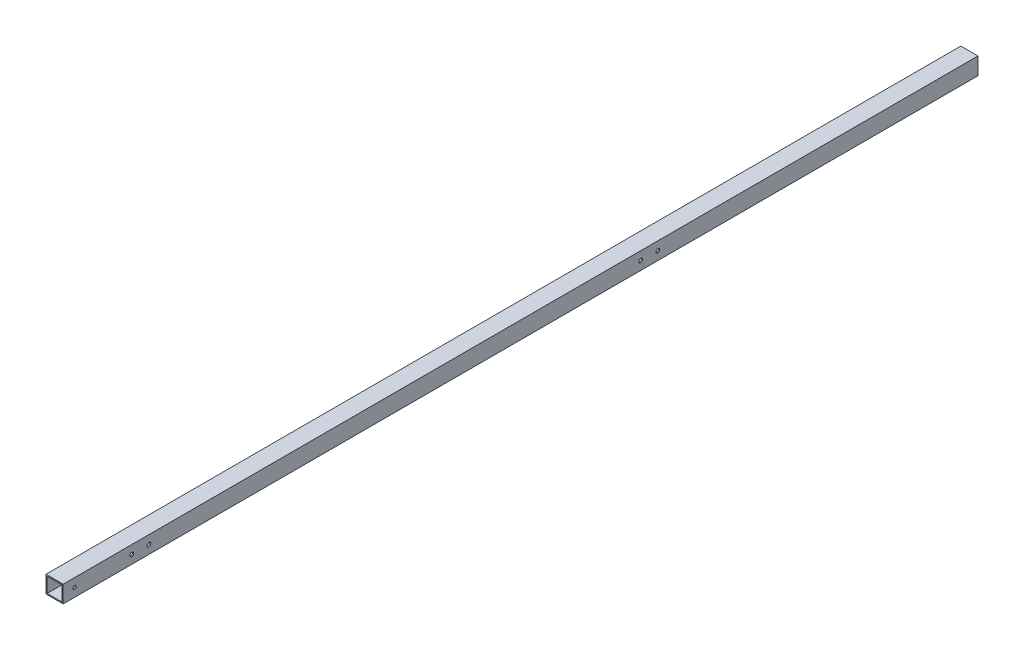
SolidWorks part; units mm, degrees
material "1060 合金"
ref_plane "前视基准面" through (0, 0, 0) normal (0, 0, 1) x (1, 0, 0)
ref_plane "上视基准面" through (0, 0, 0) normal (0, 1, 0) x (1, 0, 0)
ref_plane "右视基准面" through (0, 0, 0) normal (1, 0, 0) x (0, 0, -1)
other "Configuration Table"
sketch "草图1" plane through (0, 0, 0) normal (0, 0, 1) x (1, 0, 0)
  line L1 (0, 0) -> (15, 0)
  line L2 (0, 0) -> (0, -15)
  line L3 (0, -15) -> (15, -15)
  line L4 (15, 0) -> (15, -15)
  dimension "D1" = 15
  dimension "D2" = 15
extrude "拉伸-薄壁1" add sketch "草图1" along normal blind 800 thin thin type one direction reverse wall 1
sketch "草图2" plane through (0, -15, 0) normal (0, -1, 0) x (1, 0, 0)
  circle A1 centre (7.5, 825) radius 2.6
  circle A2 centre (7.5, 825) radius 2.6
  dimension "D1" = 0
extrude "切除-拉伸1" [suppressed] cut sketch "草图2" against normal up to next
sketch "草图3" plane through (0, 0, 0) normal (-1, 0, 0) x (0, 0, 1)
  line L0 (800, 0) -> (0, 0) construction
  line L1 (0, 0) -> (0, -15) construction
  circle A0 centre (215, -7.5) radius 1.7
  circle A1 centre (170, -7.5) radius 1.7
  dimension "D1" = 3.4
  dimension "D2" = 3.4
  dimension "D3" = 45
  dimension "D4" = 7.5
  dimension "D5" = 7.5
  dimension "D6" = 170
sketch "草图4" plane through (15, 0, 0) normal (1, 0, 0) x (0, 0, -1)
  line L0 (-800, -15) -> (0, -15) construction
  line L1 (-800, -15) -> (-800, 0) construction
  circle A0 centre (-790, -7.5) radius 1.5
  dimension "D1" = 3
  dimension "D2" = 7.5
  dimension "D3" = 10
extrude "切除-拉伸3" cut sketch "草图4" against normal through all
sketch "草图5" plane through (15, 0, 0) normal (1, 0, 0) x (0, 0, -1)
  line L0 (-800, 0) -> (0, 0) construction
  line L1 (0, -15) -> (0, 0) construction
  line L2 (-800, -1) -> (-800, -14) construction
  circle A0 centre (-280, -7.5) radius 1.65
  circle A1 centre (-295, -7.5) radius 1.65
  circle A2 centre (-725, -7.5) radius 1.65
  circle A3 centre (-740, -7.5) radius 1.65
  dimension "D1" = 3.3
  dimension "D4" = 3.3
  dimension "D7" = 7.5
  dimension "D9" = 3.3
  dimension "D10" = 3.3
  dimension "D2" = 7.5
  dimension "D3" = 15
  dimension "D5" = 7.5
  dimension "D6" = 280
  dimension "D8" = 7.5
  dimension "D11" = 15
  dimension "D12" = 60
extrude "切除-拉伸4" cut sketch "草图5" against normal through all
